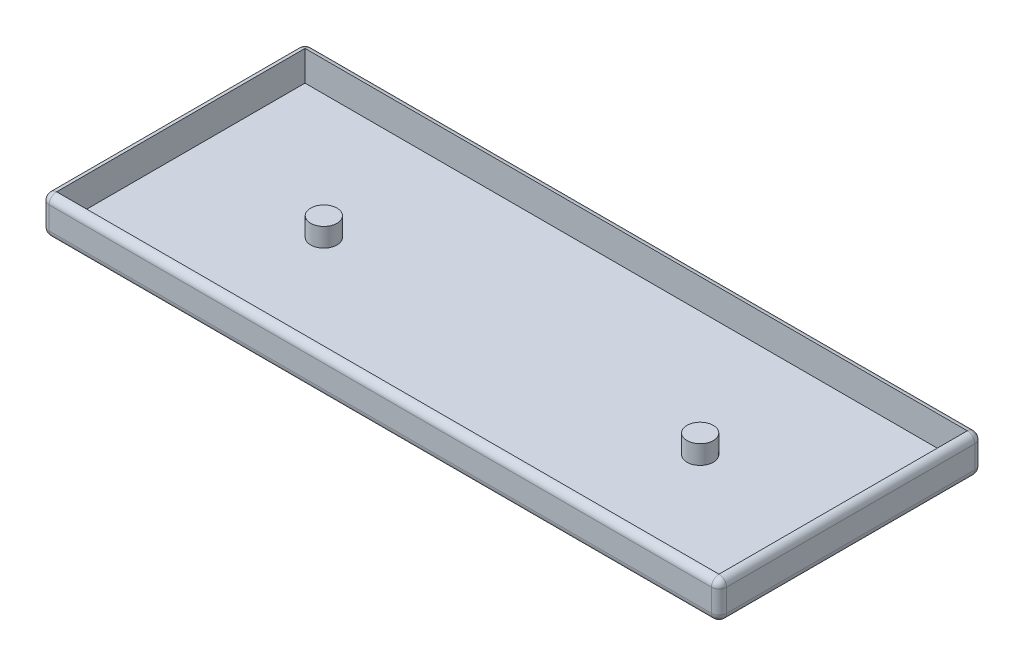
SolidWorks part; units mm, degrees
ref_plane "Front Plane" through (0, 0, 0) normal (0, 0, 1) x (1, 0, 0)
ref_plane "Top Plane" through (0, 0, 0) normal (0, 1, 0) x (1, 0, 0)
ref_plane "Right Plane" through (0, 0, 0) normal (1, 0, 0) x (0, 0, -1)
sketch "Sketch1" plane through (0, 0, 0) normal (0, 1, 0) x (1, 0, 0)
  line L1 (-90, -35) -> (90, -35)
  line L2 (-90, -35) -> (-90, 35)
  line L3 (-90, 35) -> (90, 35)
  line L4 (90, -35) -> (90, 35)
  line L5 (-90, -35) -> (90, 35) construction
  line L6 (-90, 35) -> (90, -35) construction
  point P0 (0, 0)
  dimension "D1" = 180
  dimension "D2" = 70
extrude "Boss-Extrude1" add sketch "Sketch1" along normal blind 10
sketch "Sketch2" plane through (0, 0, 0) normal (0, -1, 0) x (1, 0, 0)
  line L0 (90, 35) -> (90, -35) construction
  circle A0 centre (50, 0) radius 1.5
  dimension "D1" = 3
  dimension "D2" = 40
extrude "Cut-Extrude1" cut sketch "Sketch2" against normal blind 5
mirror "Mirror1" about plane through (0, 0, 0) normal (1, 0, 0) of "Cut-Extrude1"
fillet "Fillet1" radius 2 12 edges at (90, 0, 0) (90, 5, 35) (0, 0, 35) (-90, 5, 35) (-90, 0, 0) (0, 10, 35) (-90, 10, 0) (90, 10, 0) (90, 5, -35) (0, 10, -35) (-90, 5, -35) (0, 0, -35)
shell "Shell1" thickness 2 removed face at (0, 10, 0)
